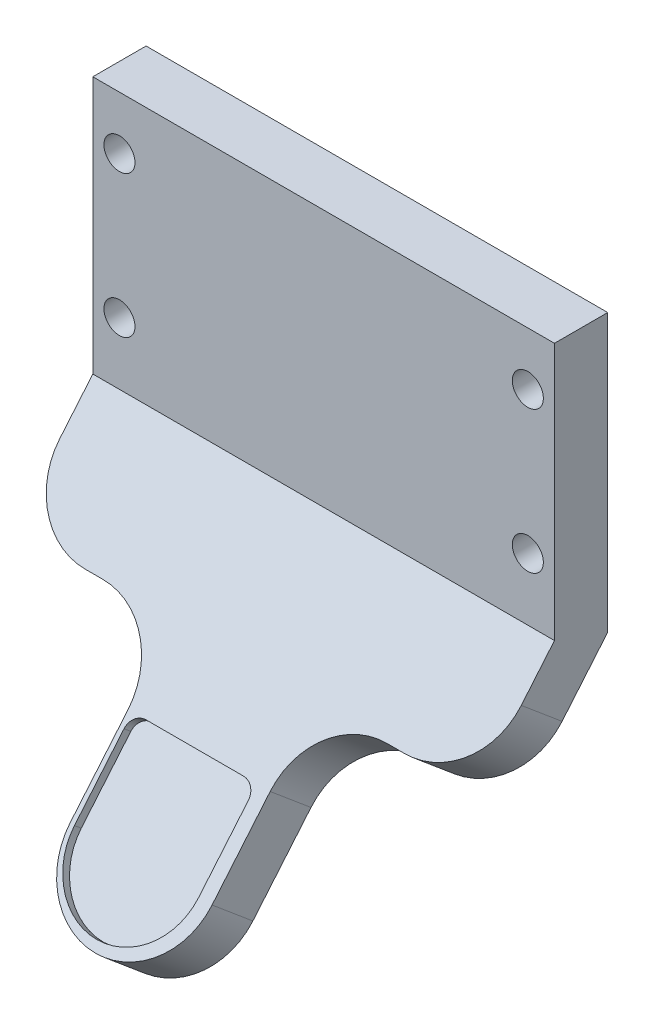
SolidWorks part; units mm, degrees
ref_plane "Plan de face" through (0, 0, 0) normal (0, 0, 1) x (1, 0, 0)
ref_plane "Plan de dessus" through (0, 0, 0) normal (0, 1, 0) x (1, 0, 0)
ref_plane "Plan de droite" through (0, 0, 0) normal (1, 0, 0) x (0, 0, -1)
sketch "Esquisse1" plane through (0, 0, 0) normal (0, 0, 1) x (1, 0, 0)
  line L1 (0, 0) -> (52, 0)
  line L2 (0, 0) -> (0, 29)
  line L3 (0, 29) -> (52, 29)
  line L4 (52, 0) -> (52, 29)
  dimension "D1" = 52
  dimension "D2" = 29
extrude "Boss.-Extru.1" add sketch "Esquisse1" along normal blind 6
sketch "Esquisse2" plane through (0, 0, 6) normal (0, 0, 1) x (1, 0, 0)
  line L0 (26, 0) -> (26, 22.4593) construction
  line L1 (0, 0) -> (52, 0) construction
  line L2 (3, 7) -> (3, 23) construction
  line L3 (0, 29) -> (0, 0) construction
  line L4 (49, 7) -> (49, 23) construction
  circle A0 centre (3, 7) radius 1.75
  circle A1 centre (3, 23) radius 1.75
  circle A2 centre (49, 23) radius 1.75
  circle A3 centre (49, 7) radius 1.75
  dimension "D4" = 3.5
  dimension "D1" = 16
  dimension "D2" = 3
  dimension "D3" = 7
extrude "Enlèv. mat.-Extru.1" cut sketch "Esquisse2" against normal through all normal cut yes
sketch "Esquisse3" plane through (0, 0, 0) normal (-1, 0, 0) x (0, 0, 1)
  line L0 (6, 0) -> (31.7115, -30.6418)
  line L1 (31.7115, -30.6418) -> (27.1152, -34.4985)
  line L2 (27.1152, -34.4985) -> (0, -2.1838)
  line L3 (0, -2.1838) -> (0, 0)
  line L5 (6, 29) -> (6, 0) construction
  line L6 (0, 0) -> (6, 0)
  dimension "D1" = 6
  dimension "D2" = 140
  dimension "D3" = 40
extrude "Boss.-Extru.2" add sketch "Esquisse3" against normal up to vertex (52 mm away) up to point (52, 29, 6)
sketch "Esquisse4" plane through (0, -0.9023, -1.0753) normal (0, -0.6428, -0.766) x (-1, 0, 0)
  line L0 (-26, -43.8567) -> (-26, -2.2151) construction
  line L1 (-52, -43.8567) -> (-34, -43.8567)
  line L2 (-52, -43.8567) -> (-52, -17.6729)
  line L3 (-52, -17.6729) -> (-34, -17.6729)
  line L4 (-34, -43.8567) -> (-34, -17.6729)
  line L5 (-52, -43.8567) -> (0, -43.8567) construction
  line L6 (-52, -1.6729) -> (0, -1.6729) construction
  line L7 (-18, -43.8567) -> (-18, -17.6729)
  line L8 (0, -17.6729) -> (-18, -17.6729)
  line L9 (0, -43.8567) -> (0, -17.6729)
  line L10 (0, -43.8567) -> (-18, -43.8567)
  dimension "D1" = 16
  dimension "D2" = 16
extrude "Enlèv. mat.-Extru.2" cut sketch "Esquisse4" against normal up to vertex (6 mm away) normal cut yes up to point (0, -30.6418, 31.7115)
fillet "Congé1" radius 8 6 edges at (18, -12.5122, 12.5827) (34, -12.5122, 12.5827) (34, -32.5701, 29.4134) (18, -32.5701, 29.4134) (52, -12.5122, 12.5827) (0, -12.5122, 12.5827)
sketch "Esquisse10" plane through (0, 2.9544, 3.5209) normal (0, 0.6428, 0.766) x (1, 0, 0)
  line L7 (18.5, -25.6729) -> (32.5, -25.6729)
  line L8 (0, -9.6729) -> (0, -3.8567) construction
  line L9 (0, -3.8567) -> (52, -3.8567) construction
  line L26 (18.5, -25.6729) -> (18.5, -35.8567)
  line L27 (32.5, -35.8567) -> (32.5, -25.6729)
  arc A21 (18.5, -35.8567) -> (25.5, -42.8567) centre (25.5, -35.8567) ccw
  arc A22 (25.5, -42.8567) -> (32.5, -35.8567) centre (25.5, -35.8567) ccw
  dimension "D1" = 7
  dimension "D2" = 18.5
  dimension "D3" = 21.8162
  dimension "D4" = 39
extrude "Enlèv. mat.-Extru.4" cut sketch "Esquisse10" against normal blind 1 normal cut yes
fillet "Congé2" radius 1.5 2 edges at (32.5, -17.0336, 19.6401) (18.5, -17.0336, 19.6401)
